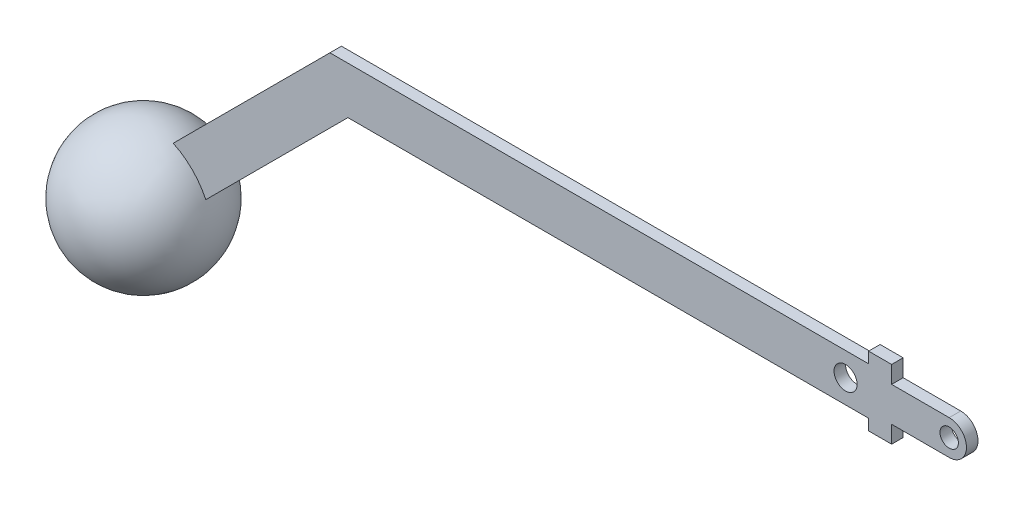
SolidWorks part; units mm, degrees
ref_plane "前视基准面" through (0, 0, 0) normal (0, 0, 1) x (1, 0, 0)
ref_plane "上视基准面" through (0, 0, 0) normal (0, 1, 0) x (1, 0, 0)
ref_plane "右视基准面" through (0, 0, 0) normal (1, 0, 0) x (0, 0, -1)
sketch "草图1" plane through (0, 0, 0) normal (0, 0, 1) x (1, 0, 0)
  line L0 (-52.6473, 0) -> (29.1954, 0) construction
  line L1 (-52.6473, 10.2348) -> (29.1954, 10.2348)
  line L2 (29.1954, 4) -> (-15.8046, 4)
  line L3 (29.1954, -10.2348) -> (-70.8046, -10.2348)
  line L4 (-52.6473, 10.2348) -> (-138.1153, 10.2348)
  line L5 (-15.8046, -4) -> (29.1954, -4)
  line L6 (-138.1153, 10.2348) -> (-260.8046, 10.2348)
  line L7 (-160.8046, -10.2348) -> (-70.8046, -10.2348)
  line L8 (-260.8046, 10.2348) -> (-260.8046, -10.2348)
  line L9 (-260.8046, -10.2348) -> (-160.8046, -10.2348)
  arc A1 (29.1954, -10.2348) -> (29.1954, 10.2348) centre (29.1954, 0) ccw
  arc A3 (29.1954, -4) -> (29.1954, 4) centre (29.1954, 0) ccw
  arc A4 (-15.8046, 4) -> (-15.8046, -4) centre (-15.8046, 0) ccw
  dimension "D1" = 100
  dimension "D2" = 100
  dimension "D3" = 4
  dimension "D4" = 8
  dimension "D5" = 45
  dimension "D6" = 90
extrude "凸台-拉伸1" add sketch "草图1" along normal blind 5
sketch "草图2" plane through (-260.8046, 0, 0) normal (-1, 0, 0) x (0, 0, 1)
  line L0 (-10.9909, 0) -> (19.2385, 0) construction
  line L1 (-17.5, 20) -> (22.5, 20)
  line L2 (-17.5, 20) -> (-17.5, -20)
  line L3 (-17.5, -20) -> (22.5, -20)
  line L4 (22.5, 20) -> (22.5, -20)
  line L5 (2.5, 11.2641) -> (2.5, -15.107) construction
  dimension "D1" = 40
  dimension "D2" = 40
  dimension "D3" = 20
  dimension "D4" = 20
extrude "凸台-拉伸2" add sketch "草图2" along normal blind 40
fillet "圆角1" radius 10 12 edges at (-260.8046, -20, 2.5) (-260.8046, 20, 2.5) (-300.8046, 20, 2.5) (-300.8046, -20, 2.5) (-280.8046, 20, -17.5) (-300.8046, 0, -17.5) (-280.8046, -20, -17.5) (-260.8046, 0, -17.5) (-280.8046, -20, 22.5) (-300.8046, 0, 22.5) (-280.8046, 20, 22.5) (-260.8046, 0, 22.5)
fillet "圆角2" radius 2 8 edges at (-260.8073, 10.2348, 2.5) (-260.8046, 0, 5) (-260.8073, -10.2348, 2.5) (-260.8046, 0, 0) (-260.8053, -10.1174, 5) (-260.8053, -10.1174, 0) (-260.8053, 10.1174, 0) (-260.8053, 10.1174, 5)
sketch "草图3" plane through (0, 0, 5) normal (0, 0, 1) x (1, 0, 0)
  line L0 (-28.8289, 10.2348) -> (-28.8289, -10.2348)
  line L1 (29.1954, 10.2348) -> (-258.8069, 10.2348) construction
  line L2 (-258.8069, -10.2348) -> (29.1954, -10.2348) construction
  line L3 (-28.8289, -10.2348) -> (29.1954, -10.2348)
  line L4 (29.1954, 10.2348) -> (-28.8289, 10.2348)
  line L5 (-15.8046, 4) -> (29.1954, 4)
  line L6 (-15.8046, -4) -> (29.1954, -4)
  arc A0 (29.1954, -10.2348) -> (29.1954, 10.2348) centre (29.1954, 0) ccw
  arc A1 (-15.8046, 4) -> (-15.8046, -4) centre (-15.8046, 0) ccw
  arc A2 (29.1954, -4) -> (29.1954, 4) centre (29.1954, 0) ccw
extrude "凸台-拉伸3" add sketch "草图3" along normal blind 20
ref_plane "基准面4" through (0, 0, 2.5) normal (0, 0, 1) x (1, 0, 0)
mirror "镜向1" about plane through (0, 0, 2.5) normal (0, 0, 1) of "凸台-拉伸3"
ref_plane "基准面5" through (60, 0, 0) normal (1, 0, 0) x (0, 0, -1)
sketch "草图4" plane through (60, 0, 0) normal (1, 0, 0) x (0, 0, -1)
  line L0 (-2.5, 24.0567) -> (-2.5, -27.5399) construction
  line L1 (-7, 10) -> (-12.5, 10) construction
  line L2 (-7.5, 10) -> (2.5, 10)
  line L3 (-7.5, 10) -> (-7.5, -10)
  line L4 (-7.5, -10) -> (2.5, -10)
  line L5 (2.5, 10) -> (2.5, -10)
  line L6 (2, -10) -> (7.5, -10) construction
  dimension "D1" = 10
  dimension "D2" = 5
extrude "切除-拉伸1" cut sketch "草图4" against normal blind 80
sketch "草图5" plane through (60, 0, 0) normal (1, 0, 0) x (0, 0, -1)
  line L0 (2.5, 10) -> (2.5, -10) construction
  line L1 (-15.5, 21.3005) -> (-30.2943, 21.3005)
  line L2 (-15.5, 21.3005) -> (-15.5, -26.781)
  line L3 (-15.5, -26.781) -> (-30.2943, -26.781)
  line L4 (-30.2943, 21.3005) -> (-30.2943, -26.781)
  line L5 (10.5, 22.9279) -> (34.6887, 22.9279)
  line L6 (10.5, 22.9279) -> (10.5, -25.0057)
  line L7 (10.5, -25.0057) -> (34.6887, -25.0057)
  line L8 (34.6887, 22.9279) -> (34.6887, -25.0057)
  line L9 (-7.5, -10) -> (-7.5, 10) construction
  dimension "D1" = 8
  dimension "D2" = 8
extrude "切除-拉伸2" cut sketch "草图5" against normal up to surface (88.8289 mm away) up to face at (-28.8289, 0, 15)
sketch "草图7" plane through (0, 0, 5) normal (0, 0, 1) x (1, 0, 0)
  line L0 (-28.8289, 10.2348) -> (-28.8289, -10.2348) construction
  circle A0 centre (-38.8289, 0) radius 5
  dimension "D1" = 10
  dimension "D2" = 10
extrude "切除-拉伸4" cut sketch "草图7" against normal through all
sketch "草图8" plane through (-20, 0, 0) normal (1, 0, 0) x (0, 0, -1)
  line L1 (-7.5, 19.816) -> (2.5, 19.816)
  line L2 (-7.5, 19.816) -> (-7.5, -21.6444)
  line L3 (-7.5, -21.6444) -> (2.5, -21.6444)
  line L4 (2.5, 19.816) -> (2.5, -21.6444)
extrude "切除-拉伸5" cut sketch "草图8" along normal blind 111
sketch "草图9" plane through (0, 0, 15.5) normal (0, 0, 1) x (1, 0, 0)
  circle A0 centre (15, 0) radius 4
  circle A1 centre (15, 0) radius 10.2348
  dimension "D1" = 15
extrude "凸台-拉伸4" add sketch "草图9" against normal up to surface (26 mm away) up to face at (6.6954, 0, -10.5)
sketch "草图10" plane through (0, 0, 15.5) normal (0, 0, 1) x (1, 0, 0)
  line L0 (15, 10.2348) -> (49.8866, 10.2348)
  line L1 (49.8866, 10.2348) -> (49.8866, -12.372)
  line L2 (49.8866, -12.372) -> (15, -10.2348)
  arc A0 (15, -10.2348) -> (15, 10.2348) centre (15, 0) ccw
extrude "切除-拉伸6" cut sketch "草图10" against normal through all
sketch "草图11" plane through (0, 0, 15.5) normal (0, 0, 1) x (1, 0, 0)
  line L0 (5.5792, 4) -> (15, 4)
  line L1 (15, 4) -> (15, -4)
  line L2 (15, -4) -> (2.5046, -4)
  line L3 (2.5046, -4) -> (2.5046, 4)
  line L4 (-15.8046, 4) -> (5.5792, 4) construction
  line L5 (2.5046, 4) -> (5.5792, 4)
  circle A0 centre (15, 0) radius 4 construction
extrude "切除-拉伸7" cut sketch "草图11" against normal through all
sketch "草图12" plane through (-20, 0, 0) normal (1, 0, 0) x (0, 0, -1)
  line L1 (-7.5, 10.2348) -> (2.5, 10.2348)
  line L2 (-7.5, 10.2348) -> (-7.5, -25.4619)
  line L3 (-7.5, -25.4619) -> (2.5, -25.4619)
  line L4 (2.5, 10.2348) -> (2.5, -25.4619)
extrude "切除-拉伸8" cut sketch "草图12" along normal blind 162
sketch "草图13" plane through (0, 0, 15.5) normal (0, 0, 1) x (1, 0, 0)
  circle A0 centre (8, 0) radius 4
  circle A1 centre (8, 0) radius 10.2348
  dimension "D1" = 8
extrude "凸台-拉伸5" add sketch "草图13" against normal up to surface (26 mm away) up to face at (-0.4023, 0, -10.5)
sketch "草图14" plane through (0, 0, 15.5) normal (0, 0, 1) x (1, 0, 0)
  line L0 (8, 10.2348) -> (37.0054, 10.2348)
  line L1 (37.0054, 10.2348) -> (37.0054, -19.761)
  line L2 (37.0054, -19.761) -> (8, -10.2348)
  arc A0 (8, -10.2348) -> (8, 10.2348) centre (8, 0) ccw
extrude "切除-拉伸9" cut sketch "草图14" against normal through all
sketch "草图15" plane through (0, 0, 15.5) normal (0, 0, 1) x (1, 0, 0)
  line L0 (-1.4208, 4) -> (8, 4)
  line L1 (8, 4) -> (8, -4)
  line L2 (8, -4) -> (-4.9507, -4)
  line L3 (-1.4208, -4) -> (-15.8046, -4) construction
  line L4 (-4.9507, -4) -> (-4.9507, 4)
  line L5 (-15.8046, 4) -> (-1.4208, 4) construction
  line L6 (-4.9507, 4) -> (-1.4208, 4)
  circle A0 centre (8, 0) radius 4 construction
extrude "切除-拉伸10" cut sketch "草图15" against normal through all
sketch "草图16" plane through (-20, 0, 0) normal (1, 0, 0) x (0, 0, -1)
  line L1 (-7.5, 10.2348) -> (2.5, 10.2348)
  line L2 (-7.5, 10.2348) -> (-7.5, -25.4479)
  line L3 (-7.5, -25.4479) -> (2.5, -25.4479)
  line L4 (2.5, 10.2348) -> (2.5, -25.4479)
extrude "切除-拉伸11" cut sketch "草图16" along normal blind 162
sketch "草图19" plane through (0, 0, 5) normal (0, 0, 1) x (1, 0, 0)
  line L0 (-258.8046, 10) -> (-258.8046, -10) construction
  line L1 (-323.1016, 37.5576) -> (-258.8046, 37.5576)
  line L2 (-323.1016, 37.5576) -> (-323.1016, -42.648)
  line L3 (-323.1016, -42.648) -> (-258.8046, -42.648)
  line L4 (-258.8046, 37.5576) -> (-258.8046, -42.648)
extrude "切除-拉伸12" cut sketch "草图19" against normal mid plane 85
sketch "草图20" plane through (0, 0, 5) normal (0, 0, 1) x (1, 0, 0)
  line L0 (-258.8046, 0) -> (-343.6574, -84.8528) construction
  line L1 (-258.8046, 10.2348) -> (-258.8046, -10.2348) construction
  line L2 (-258.8046, -10.2348) -> (-28.8289, -10.2348) construction
  line L3 (-343.6574, -84.8528) -> (-336.5863, -91.9239)
  line L4 (-343.6574, -84.8528) -> (-350.7285, -77.7817)
  line L5 (-350.7285, -77.7817) -> (-262.7119, 10.2348)
  line L6 (-336.5863, -91.9239) -> (-254.8973, -10.2348)
  line L7 (-258.8046, 10.2348) -> (-262.7119, 10.2348)
  line L8 (-258.8046, 10.2348) -> (-258.8046, -10.2348)
  line L9 (-258.8046, -10.2348) -> (-254.8973, -10.2348)
  dimension "D1" = 120
  dimension "D2" = 135
  dimension "D3" = 10
  dimension "D4" = 10
extrude "凸台-拉伸7" add sketch "草图20" against normal up to surface (5 mm away) up to face at (-33.8289, 0, 0)
sketch "草图21" plane through (0, 0, 5) normal (0, 0, 1) x (1, 0, 0)
  line L0 (-350.7285, -77.7817) -> (-336.5863, -91.9239) construction
  line L1 (-373.6574, -84.8528) -> (-313.6574, -84.8528)
  arc A0 (-313.6574, -84.8528) -> (-373.6574, -84.8528) centre (-343.6574, -84.8528) ccw
  dimension "D1" = 60
revolve "旋转2" add sketch "草图21" angle 360 about L1
sketch "草图22" plane through (0, 0, 15.5) normal (0, 0, 1) x (1, 0, 0)
  line L1 (-28.8289, 10.2348) -> (41.7107, 10.2348)
  line L2 (-28.8289, 10.2348) -> (-28.8289, -24.7247)
  line L3 (-28.8289, -24.7247) -> (41.7107, -24.7247)
  line L4 (41.7107, 10.2348) -> (41.7107, -24.7247)
extrude "切除-拉伸13" cut sketch "草图22" against normal blind 60
sketch "草图23" plane through (-28.8289, 0, 0) normal (1, 0, 0) x (0, 0, -1)
  line L0 (0, -10.2348) -> (0, -72.2389) construction
  line L1 (-5, 15) -> (0, 15)
  line L2 (-5, 15) -> (-5, -15)
  line L3 (-5, -15) -> (0, -15)
  line L4 (0, 15) -> (0, -15)
  dimension "D1" = 30
  dimension "D2" = 15
extrude "凸台-拉伸8" add sketch "草图23" along normal blind 10
sketch "草图24" plane through (-18.8289, 0, 0) normal (1, 0, 0) x (0, 0, -1)
  line L0 (0, -15) -> (0, 15) construction
  line L1 (-5, 7.5) -> (0, 7.5)
  line L2 (-5, 7.5) -> (-5, -7.5)
  line L3 (-5, -7.5) -> (0, -7.5)
  line L4 (0, 7.5) -> (0, -7.5)
  point P7 (0, 0)
  dimension "D1" = 15
  dimension "D2" = 7.5
extrude "凸台-拉伸9" add sketch "草图24" along normal blind 60
sketch "草图25" plane through (0, 0, 5) normal (0, 0, 1) x (1, 0, 0)
  line L3 (-18.8289, -7.5) -> (-18.8289, -15) construction
  circle A1 centre (6.1711, 0) radius 4
  dimension "D1" = 8
  dimension "D2" = 25
extrude "切除-拉伸14" cut sketch "草图25" against normal through all
sketch "草图27" plane through (0, 0, 5) normal (0, 0, 1) x (1, 0, 0)
  line L0 (6.1711, 7.5) -> (42.3803, 12.4684)
  line L1 (42.3803, 12.4684) -> (51.3182, -7.5)
  line L2 (51.3182, -7.5) -> (45.7545, -22.0804)
  line L3 (45.7545, -22.0804) -> (6.1711, -7.5)
  arc A0 (6.1711, -7.5) -> (6.1711, 7.5) centre (6.1711, 0) ccw
extrude "切除-拉伸16" cut sketch "草图27" against normal blind 60
